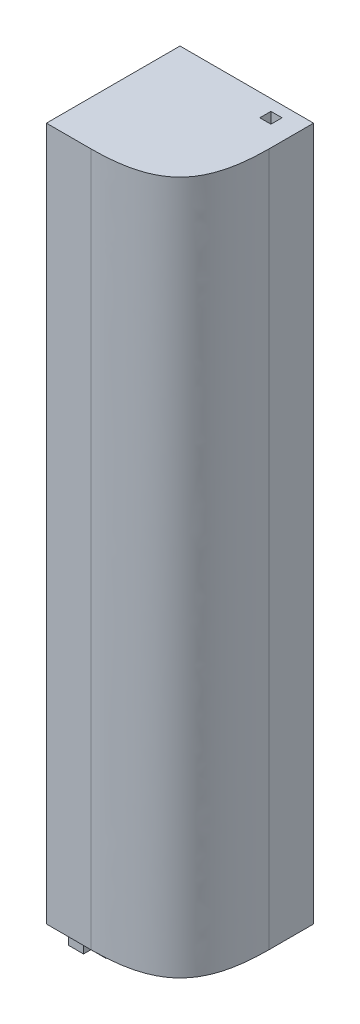
SolidWorks part; units mm, degrees
ref_plane "Front Plane" through (0, 0, 0) normal (0, 0, 1) x (1, 0, 0)
ref_plane "Top Plane" through (0, 0, 0) normal (0, 1, 0) x (1, 0, 0)
ref_plane "Right Plane" through (0, 0, 0) normal (1, 0, 0) x (0, 0, -1)
sketch "Sketch1" plane through (0, 0, 0) normal (0, 1, 0) x (1, 0, 0)
  line L1 (0, 0) -> (36, 0)
  line L2 (0, 0) -> (0, 36)
  line L3 (0, 36) -> (36, 36)
  line L4 (36, 0) -> (36, 36)
  dimension "D1" = 36
  dimension "D2" = 36
extrude "Boss-Extrude1" add sketch "Sketch1" along normal blind 186.9
fillet "Fillet1" radius 24 1 edges at (36, 93.45, 0) conic rho 0.55
sketch "Sketch2" plane through (0, 0, 0) normal (0, -1, 0) x (1, 0, 0)
  line L0 (36, -24) -> (36, -36) construction
  line L1 (0, -12.5) -> (14.28, -12.5)
  line L2 (0, -12.5) -> (0, -36)
  line L3 (0, -36) -> (14.28, -36)
  line L4 (14.28, -12.5) -> (14.28, -36)
  line L5 (0, 0) -> (12, 0) construction
  line L6 (0, -36) -> (0, 0) construction
  line L7 (36, -36) -> (0, -36) construction
  dimension "D1" = 21.72
  dimension "D2" = 12.5
  dimension "D3" = 0
  dimension "D4" = 0
extrude "Cut-Extrude1" cut sketch "Sketch2" against normal blind 27
sketch "Sketch3" plane through (0, 27, 0) normal (0, -1, 0) x (1, 0, 0)
  line L0 (0, -12.5) -> (0, -36) construction
  line L1 (0, -15) -> (11.78, -15)
  line L2 (0, -15) -> (0, -36)
  line L3 (0, -36) -> (11.78, -36)
  line L4 (11.78, -15) -> (11.78, -36)
  line L5 (0, -36) -> (14.28, -36) construction
  line L6 (14.28, -12.5) -> (0, -12.5) construction
  line L7 (14.28, -36) -> (14.28, -12.5) construction
  dimension "D1" = 2.5
  dimension "D2" = 2.5
extrude "Cut-Extrude2" cut sketch "Sketch3" against normal blind 8
sketch "Sketch4" plane through (0, 0, 0) normal (0, -1, 0) x (1, 0, 0)
  line L0 (36, -24) -> (36, -36) construction
  line L1 (0, 0) -> (12, 0) construction
  circle A0 centre (21, -15) radius 2
  dimension "D1" = 4
  dimension "D2" = 15
  dimension "D3" = 15
extrude "Cut-Extrude3" cut sketch "Sketch4" against normal blind 5
sketch "Sketch5" plane through (0, 0, 0) normal (0, -1, 0) x (1, 0, 0)
  line L0 (36, -24) -> (36, -36) construction
  line L1 (18.28, -28) -> (22.28, -28)
  line L2 (18.28, -28) -> (18.28, -32)
  line L3 (18.28, -32) -> (32, -32)
  line L4 (32, -28) -> (32, -32)
  line L5 (36, -36) -> (14.28, -36) construction
  line L6 (14.28, -36) -> (14.28, -12.5) construction
  line L7 (0, 0) -> (12, 0) construction
  line L8 (4, -2) -> (8, -2)
  line L9 (4, -2) -> (4, -10.5)
  line L10 (4, -10.5) -> (8, -10.5)
  line L11 (8, -2) -> (8, -4)
  line L12 (14.28, -12.5) -> (0, -12.5) construction
  line L13 (0, -12.5) -> (0, 0) construction
  line L14 (8, -8.5) -> (8, -10.5)
  line L15 (8, -4) -> (12, -4)
  line L17 (8, -8.5) -> (12, -8.5)
  line L18 (12, -4) -> (12, -8.5)
  line L20 (22.28, -28) -> (22.28, -24)
  line L21 (22.28, -24) -> (28, -24)
  line L22 (28, -28) -> (28, -24)
  line L23 (28, -28) -> (32, -28)
  dimension "D1" = 4
  dimension "D2" = 4
  dimension "D3" = 4
  dimension "D4" = 4
  dimension "D5" = 2
  dimension "D6" = 2
  dimension "D7" = 4
  dimension "D8" = 4
  dimension "D9" = 2
  dimension "D10" = 2
  dimension "D11" = 4
  dimension "D12" = 4
  dimension "D13" = 4
  dimension "D14" = 4
  dimension "D15" = 24
  dimension "D16" = 24
extrude "Boss-Extrude2" add sketch "Sketch5" along normal blind 4
sketch "Sketch6" plane through (0, 0, -36) normal (0, 0, -1) x (-1, 0, 0)
  line L0 (-36, 186.9) -> (0, 186.9) construction
  line L1 (-32, 182.9) -> (-26, 182.9)
  line L2 (-32, 182.9) -> (-32, 178.9)
  line L3 (-32, 178.9) -> (-26, 178.9)
  line L4 (-26, 182.9) -> (-26, 178.9)
  line L5 (-36, 186.9) -> (-36, 0) construction
  dimension "D1" = 4
  dimension "D2" = 4
  dimension "D3" = 6
  dimension "D4" = 4
extrude "Cut-Extrude4" cut sketch "Sketch6" against normal blind 9
sketch "Sketch7" plane through (0, 186.9, 0) normal (0, 1, 0) x (1, 0, 0)
  line L0 (36, 36) -> (0, 36) construction
  line L1 (27.5, 33) -> (30.5, 33)
  line L2 (27.5, 33) -> (27.5, 30)
  line L3 (27.5, 30) -> (30.5, 30)
  line L4 (30.5, 33) -> (30.5, 30)
  line L5 (36, 24) -> (36, 36) construction
  dimension "D1" = 3
  dimension "D2" = 3
  dimension "D3" = 3
  dimension "D4" = 5.5
extrude "Cut-Extrude5" cut sketch "Sketch7" against normal blind 10
